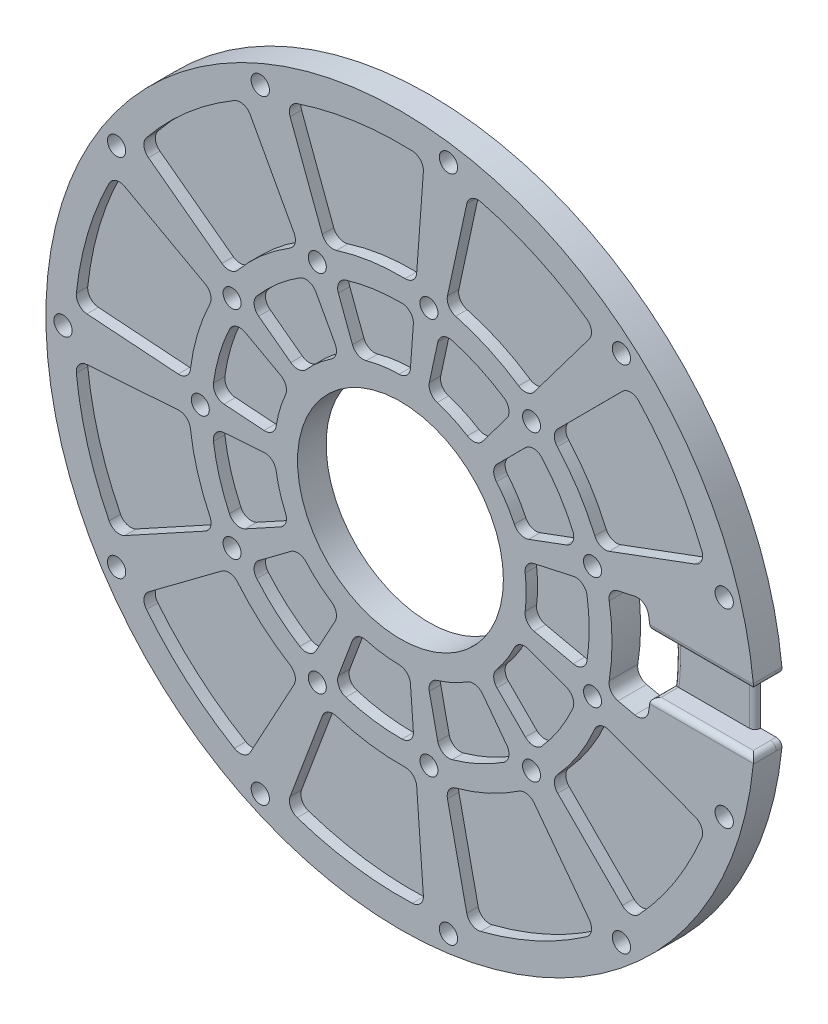
SolidWorks part; units mm, degrees
material "ABS"
ref_plane "Front Plane" through (0, 0, 0) normal (0, 0, 1) x (1, 0, 0)
ref_plane "Top Plane" through (0, 0, 0) normal (0, 1, 0) x (1, 0, 0)
ref_plane "Right Plane" through (0, 0, 0) normal (1, 0, 0) x (0, 0, -1)
sketch "Sketch1" plane through (0, 0, -61.9958) normal (0, 0, 1) x (1, 0, 0)
  circle A0 centre (89.0728, 47.2587) radius 62
  circle A2 centre (89.0728, 47.2587) radius 18
  dimension "D1" = 124
  dimension "D2" = 36
extrude "Boss-Extrude1" add sketch "Sketch1" along normal blind 5
sketch "Sketch2" plane through (0, 0, -56.9958) normal (0, 0, 1) x (1, 0, 0)
  line L0 (89.0728, 47.2587) -> (54.0728, 47.2587) construction
  circle A0 centre (54.0728, 47.2587) radius 1.575
  circle A1 centre (59.6289, 66.1811) radius 1.575
  circle A2 centre (74.5333, 79.0958) radius 1.575
  circle A3 centre (94.0538, 81.9025) radius 1.575
  circle A4 centre (111.9929, 73.7099) radius 1.575
  circle A5 centre (122.655, 57.1193) radius 1.575
  circle A6 centre (122.655, 37.3981) radius 1.575
  circle A7 centre (111.9929, 20.8075) radius 1.575
  circle A8 centre (94.0538, 12.615) radius 1.575
  circle A9 centre (74.5333, 15.4216) radius 1.575
  circle A10 centre (59.6289, 28.3363) radius 1.575
  point P27 (89.0728, 47.2587)
  dimension "D2" = 3.15
  dimension "D3" = 11
  dimension "D1" = 35
extrude "Cut-Extrude1" cut sketch "Sketch2" against normal through all
sketch "Sketch4" plane through (0, 0, -56.9958) normal (0, 0, 1) x (1, 0, 0)
  line L0 (89.0728, 47.2587) -> (30.0728, 47.2587) construction
  circle A0 centre (30.0728, 47.2587) radius 1.6
  circle A1 centre (39.4388, 79.1565) radius 1.6
  circle A2 centre (64.5633, 100.927) radius 1.6
  circle A3 centre (97.4694, 105.6582) radius 1.6
  circle A4 centre (127.7096, 91.8479) radius 1.6
  circle A5 centre (145.6829, 63.8809) radius 1.6
  circle A6 centre (145.6829, 30.6365) radius 1.6
  circle A7 centre (127.7096, 2.6695) radius 1.6
  circle A8 centre (97.4694, -11.1408) radius 1.6
  circle A9 centre (64.5633, -6.4096) radius 1.6
  circle A10 centre (39.4388, 15.3609) radius 1.6
  point P28 (89.0728, 47.2587)
  dimension "D2" = 3.2
  dimension "D1" = 59
  dimension "D3" = 11
extrude "Cut-Extrude3" cut sketch "Sketch4" against normal through all
sketch "Sketch3" plane through (0, 0, -56.9958) normal (0, 0, 1) x (1, 0, 0)
  line L0 (89.0728, 47.2587) -> (94.0538, 81.9025) construction
  line L1 (89.0728, 47.2587) -> (74.5333, 79.0958) construction
  line L2 (78.216, 76.2264) -> (80.6793, 69.654)
  line L3 (91.3287, 78.1118) -> (90.8168, 71.1116)
  line L44 (89.0728, 47.2587) -> (64.5633, 100.927) construction
  line L45 (89.0728, 47.2587) -> (97.4694, 105.6582) construction
  line L46 (75.4037, 83.73) -> (69.7833, 98.7263)
  line L47 (93.0808, 102.076) -> (91.913, 86.1037)
  line L52 (127.1182, 55.5982) -> (130.0522, 56.2414)
  line L53 (130.0522, 38.2761) -> (127.1182, 38.9192)
  line L68 (122.081, 91.207) -> (112.4633, 78.4017)
  line L69 (97.2915, 85.3304) -> (100.6709, 100.9847)
  line L70 (140.6014, 66.3848) -> (125.5873, 60.812)
  line L71 (116.5699, 74.8433) -> (127.8762, 86.1855)
  line L72 (142.7617, 35.4901) -> (127.1182, 38.9192) [skipped]
  line L73 (127.1182, 55.5982) -> (142.7617, 59.0273) [skipped]
  line L74 (127.8762, 8.3319) -> (116.5699, 19.6742)
  line L75 (125.5873, 33.7055) -> (140.6014, 28.1326)
  line L76 (100.6709, -6.4673) -> (97.2915, 9.187)
  line L77 (112.4633, 16.1158) -> (122.081, 3.3104)
  line L78 (69.7833, -4.2089) -> (75.4037, 10.7874)
  line L79 (91.913, 8.4137) -> (93.0808, -7.5586)
  line L80 (45.0199, 14.3901) -> (57.8558, 23.9671)
  line L81 (70.4609, 13.0447) -> (62.8081, -1.0234)
  line L82 (34.2431, 43.4246) -> (50.219, 44.5418)
  line L83 (54.918, 28.5384) -> (40.8742, 20.8409)
  line L84 (40.8742, 73.6765) -> (54.918, 65.979)
  line L85 (50.219, 49.9756) -> (34.2431, 51.0928)
  line L86 (62.8081, 95.5409) -> (70.4609, 81.4727)
  line L87 (57.8558, 70.5503) -> (45.0199, 80.1273)
  line L88 (95.6006, 77.4975) -> (94.1195, 70.6367)
  line L89 (107.651, 71.9943) -> (103.4358, 66.3821)
  line L90 (110.9127, 69.168) -> (105.9575, 64.1971)
  line L91 (118.0748, 58.0235) -> (111.4946, 55.5811)
  line L92 (119.2908, 53.8825) -> (112.4347, 52.3796)
  line L93 (119.2908, 40.635) -> (112.4347, 42.1378)
  line L94 (118.0748, 36.4939) -> (111.4946, 38.9363)
  line L95 (110.9127, 25.3494) -> (105.9575, 30.3204)
  line L96 (107.651, 22.5231) -> (103.4358, 28.1353)
  line L97 (95.6006, 17.0199) -> (94.1195, 23.8807)
  line L98 (91.3287, 16.4057) -> (90.8168, 23.4059)
  line L99 (78.216, 18.291) -> (80.6793, 24.8634)
  line L100 (74.2901, 20.0839) -> (77.6441, 26.2495)
  line L101 (64.2783, 28.7591) -> (69.9039, 32.9565)
  line L102 (61.945, 32.3899) -> (68.1, 35.7634)
  line L103 (58.2127, 45.1008) -> (65.2145, 45.5904)
  line L104 (58.2127, 49.4167) -> (65.2145, 48.927)
  line L105 (61.945, 62.1275) -> (68.1, 58.754)
  line L106 (64.2783, 65.7583) -> (69.9039, 61.5609)
  line L107 (74.2901, 74.4336) -> (77.6441, 68.2679)
  arc A0 (88.843, 69.2575) -> (83.0955, 68.4311) centre (89.0728, 47.2587) ccw
  arc A1 (89.3508, 80.2575) -> (79.5092, 78.8425) centre (89.0728, 47.2587) ccw
  arc A22 (91.3287, 78.1118) -> (89.3508, 80.2575) centre (89.334, 78.2576) ccw
  arc A23 (78.216, 76.2264) -> (79.5092, 78.8425) centre (80.0888, 76.9283) cw
  arc A24 (80.6793, 69.654) -> (83.0955, 68.4311) centre (82.5521, 70.3559) ccw
  arc A25 (90.8168, 71.1116) -> (88.843, 69.2575) centre (88.8222, 71.2574) cw
  arc A86 (77.8815, 82.5256) -> (89.875, 84.25) centre (89.0728, 47.2587) cw
  arc A87 (71.0227, 101.3253) -> (91.1594, 104.2205) centre (89.0728, 47.2587) cw
  arc A88 (91.913, 86.1037) -> (89.875, 84.25) centre (89.9183, 86.2495) cw
  arc A89 (93.0808, 102.076) -> (91.1594, 104.2205) centre (91.0862, 102.2218) ccw
  arc A90 (69.7833, 98.7263) -> (71.0227, 101.3253) centre (71.6561, 99.4282) cw
  arc A91 (75.4037, 83.73) -> (77.8815, 82.5256) centre (77.2765, 84.4319) ccw
  arc A104 (132.4522, 54.6225) -> (132.4522, 39.895) centre (89.0728, 47.2587) cw
  arc A106 (127.1182, 55.5982) -> (125.5734, 53.3171) centre (127.5464, 53.6446) ccw
  arc A107 (125.5734, 53.3171) -> (125.5734, 41.2003) centre (89.0728, 47.2587) cw
  arc A108 (127.1182, 38.9192) -> (125.5734, 41.2003) centre (127.5464, 40.8728) cw
  arc A152 (132.4522, 54.6225) -> (130.0522, 56.2414) centre (130.4804, 54.2877) ccw
  arc A153 (132.4522, 39.895) -> (130.0522, 38.2761) centre (130.4804, 40.2297) cw
  arc A154 (122.081, 91.207) -> (121.624, 94.0499) centre (120.4819, 92.4081) ccw
  arc A155 (103.1187, 102.501) -> (121.624, 94.0499) centre (89.0728, 47.2587) cw
  arc A156 (100.6709, 100.9847) -> (103.1187, 102.501) centre (102.6259, 100.5627) cw
  arc A157 (97.2915, 85.3304) -> (98.7248, 82.9776) centre (99.2465, 84.9084) ccw
  arc A158 (98.7248, 82.9776) -> (109.7466, 77.9441) centre (89.0728, 47.2587) cw
  arc A159 (112.4633, 78.4017) -> (109.7466, 77.9441) centre (110.8641, 79.6028) cw
  arc A160 (140.6014, 66.3848) -> (141.7539, 69.0235) centre (139.9054, 68.2598) ccw
  arc A161 (130.7552, 86.1377) -> (141.7539, 69.0235) centre (89.0728, 47.2587) cw
  arc A162 (127.8762, 86.1855) -> (130.7552, 86.1377) centre (129.2927, 84.7735) cw
  arc A163 (116.5699, 74.8433) -> (116.5036, 72.0891) centre (117.9864, 73.4313) ccw
  arc A164 (116.5036, 72.0891) -> (123.0545, 61.8958) centre (89.0728, 47.2587) cw
  arc A165 (125.5873, 60.812) -> (123.0545, 61.8958) centre (124.8913, 62.687) cw
  arc A166 (142.7617, 35.4901) -> (145.1578, 37.0869) centre (143.19, 37.4438) ccw [skipped]
  arc A167 (145.1578, 57.4306) -> (145.1578, 37.0869) centre (89.0728, 47.2587) cw [skipped]
  arc A168 (142.7617, 59.0273) -> (145.1578, 57.4306) centre (143.19, 57.0737) cw [skipped]
  arc A169 (127.1182, 55.5982) -> (125.5734, 53.3171) centre (127.5464, 53.6446) ccw [skipped]
  arc A170 (125.5734, 53.3171) -> (125.5734, 41.2003) centre (89.0728, 47.2587) cw [skipped]
  arc A171 (127.1182, 38.9192) -> (125.5734, 41.2003) centre (127.5464, 40.8728) cw [skipped]
  arc A172 (127.8762, 8.3319) -> (130.7552, 8.3797) centre (129.2927, 9.7439) ccw
  arc A173 (141.7539, 25.4939) -> (130.7552, 8.3797) centre (89.0728, 47.2587) cw
  arc A174 (140.6014, 28.1326) -> (141.7539, 25.4939) centre (139.9054, 26.2576) cw
  arc A175 (125.5873, 33.7055) -> (123.0545, 32.6216) centre (124.8913, 31.8305) ccw
  arc A176 (123.0545, 32.6216) -> (116.5036, 22.4283) centre (89.0728, 47.2587) cw
  arc A177 (116.5699, 19.6742) -> (116.5036, 22.4283) centre (117.9864, 21.0861) cw
  arc A178 (100.6709, -6.4673) -> (103.1187, -7.9836) centre (102.6259, -6.0453) ccw
  arc A179 (121.624, 0.4675) -> (103.1187, -7.9836) centre (89.0728, 47.2587) cw
  arc A180 (122.081, 3.3104) -> (121.624, 0.4675) centre (120.4819, 2.1093) cw
  arc A181 (112.4633, 16.1158) -> (109.7466, 16.5733) centre (110.8641, 14.9147) ccw
  arc A182 (109.7466, 16.5733) -> (98.7248, 11.5398) centre (89.0728, 47.2587) cw
  arc A183 (97.2915, 9.187) -> (98.7248, 11.5398) centre (99.2465, 9.6091) cw
  arc A184 (69.7833, -4.2089) -> (71.0227, -6.8079) centre (71.6561, -4.9108) ccw
  arc A185 (91.1594, -9.7031) -> (71.0227, -6.8079) centre (89.0728, 47.2587) cw
  arc A186 (93.0808, -7.5586) -> (91.1594, -9.7031) centre (91.0862, -7.7044) cw
  arc A187 (91.913, 8.4137) -> (89.875, 10.2674) centre (89.9183, 8.2679) ccw
  arc A188 (89.875, 10.2674) -> (77.8815, 11.9918) centre (89.0728, 47.2587) cw
  arc A189 (75.4037, 10.7874) -> (77.8815, 11.9918) centre (77.2765, 10.0855) cw
  arc A190 (45.0199, 14.3901) -> (44.6575, 11.5336) centre (46.216, 12.7871) ccw
  arc A191 (60.0323, -1.7887) -> (44.6575, 11.5336) centre (89.0728, 47.2587) cw
  arc A192 (62.8081, -1.0234) -> (60.0323, -1.7887) centre (61.0512, -0.0677) cw
  arc A193 (70.4609, 13.0447) -> (69.7486, 15.706) centre (68.7041, 14.0004) ccw
  arc A194 (69.7486, 15.706) -> (60.5913, 23.6408) centre (89.0728, 47.2587) cw
  arc A195 (57.8558, 23.9671) -> (60.5913, 23.6408) centre (59.0518, 22.3642) cw
  arc A196 (34.2431, 43.4246) -> (32.3938, 41.2175) centre (34.3826, 41.4295) ccw
  arc A197 (38.1253, 21.6979) -> (32.3938, 41.2175) centre (89.0728, 47.2587) cw
  arc A198 (40.8742, 20.8409) -> (38.1253, 21.6979) centre (39.9129, 22.5948) cw
  arc A199 (54.918, 28.5384) -> (55.7576, 31.1623) centre (53.9567, 30.2922) ccw
  arc A200 (55.7576, 31.1623) -> (52.3438, 42.7883) centre (89.0728, 47.2587) cw
  arc A201 (50.219, 44.5418) -> (52.3438, 42.7883) centre (50.3585, 42.5467) cw
  arc A202 (40.8742, 73.6765) -> (38.1253, 72.8195) centre (39.9129, 71.9226) ccw
  arc A203 (32.3938, 53.2999) -> (38.1253, 72.8195) centre (89.0728, 47.2587) cw
  arc A204 (34.2431, 51.0928) -> (32.3938, 53.2999) centre (34.3826, 53.0879) cw
  arc A205 (50.219, 49.9756) -> (52.3438, 51.7291) centre (50.3585, 51.9708) ccw
  arc A206 (52.3438, 51.7291) -> (55.7576, 63.3551) centre (89.0728, 47.2587) cw
  arc A207 (54.918, 65.979) -> (55.7576, 63.3551) centre (53.9567, 64.2252) cw
  arc A208 (62.8081, 95.5409) -> (60.0323, 96.3061) centre (61.0512, 94.5851) ccw
  arc A209 (44.6575, 82.9838) -> (60.0323, 96.3061) centre (89.0728, 47.2587) cw
  arc A210 (45.0199, 80.1273) -> (44.6575, 82.9838) centre (46.216, 81.7303) cw
  arc A211 (57.8558, 70.5503) -> (60.5913, 70.8766) centre (59.0518, 72.1533) ccw
  arc A212 (60.5913, 70.8766) -> (69.7486, 78.8115) centre (89.0728, 47.2587) cw
  arc A213 (70.4609, 81.4727) -> (69.7486, 78.8115) centre (68.7041, 80.517) cw
  arc A214 (107.1472, 74.8688) -> (98.1029, 78.9992) centre (89.0728, 47.2587) ccw
  arc A215 (95.6006, 77.4975) -> (98.1029, 78.9992) centre (97.5556, 77.0755) cw
  arc A216 (100.773, 65.8895) -> (95.491, 68.3017) centre (89.0728, 47.2587) ccw
  arc A217 (94.1195, 70.6367) -> (95.491, 68.3017) centre (96.0745, 70.2147) ccw
  arc A218 (103.4358, 66.3821) -> (100.773, 65.8895) centre (101.8366, 67.5832) cw
  arc A219 (107.651, 71.9943) -> (107.1472, 74.8688) centre (106.0518, 73.1954) ccw
  arc A220 (119.2051, 60.714) -> (113.8296, 69.0785) centre (89.0728, 47.2587) ccw
  arc A221 (110.9127, 69.168) -> (113.8296, 69.0785) centre (112.3292, 67.7561) cw
  arc A222 (108.9882, 56.6063) -> (105.8488, 61.4912) centre (89.0728, 47.2587) ccw
  arc A223 (105.9575, 64.1971) -> (105.8488, 61.4912) centre (107.3739, 62.7851) ccw
  arc A224 (111.4946, 55.5811) -> (108.9882, 56.6063) centre (110.7986, 57.4561) cw
  arc A225 (118.0748, 58.0235) -> (119.2051, 60.714) centre (117.3789, 59.8985) ccw
  arc A226 (121.6962, 42.2873) -> (121.6962, 52.2301) centre (89.0728, 47.2587) ccw
  arc A227 (119.2908, 53.8825) -> (121.6962, 52.2301) centre (119.719, 51.9288) cw
  arc A228 (110.8804, 44.3554) -> (110.8804, 50.162) centre (89.0728, 47.2587) ccw
  arc A229 (112.4347, 52.3796) -> (110.8804, 50.162) centre (112.8629, 50.426) ccw
  arc A230 (112.4347, 42.1378) -> (110.8804, 44.3554) centre (112.8629, 44.0914) cw
  arc A231 (119.2908, 40.635) -> (121.6962, 42.2873) centre (119.719, 42.5886) ccw
  arc A232 (113.8296, 25.4389) -> (119.2051, 33.8034) centre (89.0728, 47.2587) ccw
  arc A233 (118.0748, 36.4939) -> (119.2051, 33.8034) centre (117.3789, 34.6189) cw
  arc A234 (105.8488, 33.0262) -> (108.9882, 37.9111) centre (89.0728, 47.2587) ccw
  arc A235 (111.4946, 38.9363) -> (108.9882, 37.9111) centre (110.7986, 37.0613) ccw
  arc A236 (105.9575, 30.3204) -> (105.8488, 33.0262) centre (107.3739, 31.7323) cw
  arc A237 (110.9127, 25.3494) -> (113.8296, 25.4389) centre (112.3292, 26.7614) ccw
  arc A238 (98.1029, 15.5182) -> (107.1472, 19.6486) centre (89.0728, 47.2587) ccw
  arc A239 (107.651, 22.5231) -> (107.1472, 19.6486) centre (106.0518, 21.322) cw
  arc A240 (95.491, 26.2157) -> (100.773, 28.6279) centre (89.0728, 47.2587) ccw
  arc A241 (103.4358, 28.1353) -> (100.773, 28.6279) centre (101.8366, 26.9342) ccw
  arc A242 (94.1195, 23.8807) -> (95.491, 26.2157) centre (96.0745, 24.3027) cw
  arc A243 (95.6006, 17.0199) -> (98.1029, 15.5182) centre (97.5556, 17.4419) ccw
  arc A244 (79.5092, 15.6749) -> (89.3508, 14.2599) centre (89.0728, 47.2587) ccw
  arc A245 (91.3287, 16.4057) -> (89.3508, 14.2599) centre (89.334, 16.2598) cw
  arc A246 (83.0955, 26.0863) -> (88.843, 25.2599) centre (89.0728, 47.2587) ccw
  arc A247 (90.8168, 23.4059) -> (88.843, 25.2599) centre (88.8222, 23.26) ccw
  arc A248 (80.6793, 24.8634) -> (83.0955, 26.0863) centre (82.5521, 24.1615) cw
  arc A249 (78.216, 18.291) -> (79.5092, 15.6749) centre (80.0888, 17.5891) ccw
  arc A250 (63.9519, 25.8592) -> (71.4662, 19.348) centre (89.0728, 47.2587) ccw
  arc A251 (74.2901, 20.0839) -> (71.4662, 19.348) centre (72.5332, 21.0396) cw
  arc A252 (72.5977, 32.6789) -> (76.9861, 28.8764) centre (89.0728, 47.2587) ccw
  arc A253 (77.6441, 26.2495) -> (76.9861, 28.8764) centre (75.8873, 27.2052) ccw
  arc A254 (69.9039, 32.9565) -> (72.5977, 32.6789) centre (71.0999, 31.3535) cw
  arc A255 (64.2783, 28.7591) -> (63.9519, 25.8592) centre (65.4743, 27.1561) ccw
  arc A256 (56.3703, 42.8377) -> (59.1715, 33.2976) centre (89.0728, 47.2587) ccw
  arc A257 (61.945, 32.3899) -> (59.1715, 33.2976) centre (60.9837, 34.1437) cw
  arc A258 (67.3306, 43.9005) -> (68.9665, 38.3291) centre (89.0728, 47.2587) ccw
  arc A259 (68.1, 35.7634) -> (68.9665, 38.3291) centre (67.1387, 37.5173) ccw
  arc A260 (65.2145, 45.5904) -> (67.3306, 43.9005) centre (65.354, 43.5952) cw
  arc A261 (58.2127, 45.1008) -> (56.3703, 42.8377) centre (58.3522, 43.1056) ccw
  arc A262 (59.1715, 61.2198) -> (56.3703, 51.6797) centre (89.0728, 47.2587) ccw
  arc A263 (58.2127, 49.4167) -> (56.3703, 51.6797) centre (58.3522, 51.4118) cw
  arc A264 (68.9665, 56.1883) -> (67.3306, 50.6169) centre (89.0728, 47.2587) ccw
  arc A265 (65.2145, 48.927) -> (67.3306, 50.6169) centre (65.354, 50.9222) ccw
  arc A266 (68.1, 58.754) -> (68.9665, 56.1883) centre (67.1387, 57.0001) cw
  arc A267 (61.945, 62.1275) -> (59.1715, 61.2198) centre (60.9837, 60.3737) ccw
  arc A268 (71.4662, 75.1694) -> (63.9519, 68.6582) centre (89.0728, 47.2587) ccw
  arc A269 (64.2783, 65.7583) -> (63.9519, 68.6582) centre (65.4743, 67.3613) cw
  arc A270 (76.9861, 65.6411) -> (72.5977, 61.8385) centre (89.0728, 47.2587) ccw
  arc A271 (69.9039, 61.5609) -> (72.5977, 61.8385) centre (71.0999, 63.1639) ccw
  arc A272 (77.6441, 68.2679) -> (76.9861, 65.6411) centre (75.8873, 67.3122) cw
  arc A273 (74.2901, 74.4336) -> (71.4662, 75.1694) centre (72.5332, 73.4779) ccw
  point P52 (89.0728, 47.2587)
  point P142 (89.0728, 47.2587)
  point P291 (89.0728, 47.2587)
  point P293 (89.0728, 47.2587)
  dimension "D1" = 33
  dimension "D2" = 22
  dimension "D5" = 44
  dimension "D6" = 6.5725
  dimension "D7" = 57
  dimension "D8" = 37
  dimension "D11" = 2
  dimension "D12" = 2
  dimension "D13" = 11
  dimension "D14" = 3.0037
  dimension "D10" = 15.9723
  dimension "D4" = 7.0002
  dimension "D3" = 2
  dimension "D15" = 37
  dimension "D16" = 11
  dimension "D9" = 4
extrude "Cut-Extrude2" cut sketch "Sketch3" against normal blind 2
extrude "Cut-Extrude5" cut sketch "Sketch3<3>" against normal through all contours A153 A104 A152 L52 A106 A107 A108 L53 region at (129.3712, 47.2587, -56.9958)
sketch "Sketch3<3>" plane through (0, 0, -56.9958) normal (0, 0, 1) x (1, 0, 0) same geometry as "Sketch3"
sketch "Sketch7" plane through (0, 0, -56.9958) normal (0, 0, 1) x (1, 0, 0)
  line L0 (133.0728, 47.2587) -> (151.0728, 47.2587) construction
  line L1 (132.7878, 52.2587) -> (151.0728, 52.2587)
  line L2 (132.7878, 42.2587) -> (151.0728, 42.2587)
  line L3 (132.7878, 52.2587) -> (132.7878, 42.2587)
  line L4 (151.0728, 47.2587) -> (151.0728, 52.2587)
  line L5 (151.0728, 47.2587) -> (151.0728, 42.2587)
  arc A0 (132.4522, 39.895) -> (132.4522, 54.6225) centre (89.0728, 47.2587) ccw construction
  circle A1 centre (89.0728, 47.2587) radius 62 construction
  dimension "D1" = 5
  dimension "D2" = 5
extrude "Cut-Extrude6" cut sketch "Sketch7" against normal blind 4 contours L4 L1 L3 L2 L5
fillet "Fillet1" radius 1 7 edges at (132.7878, 42.2587, -58.9958) (150.8709, 42.2587, -58.9958) (132.7878, 52.2587, -58.9958) (150.8709, 52.2587, -58.9958) (133.0728, 47.2587, -60.9958) (141.8293, 52.2587, -56.9958) (141.8293, 42.2587, -56.9958)
sketch "Sketch8" plane through (0, 0, -60.9958) normal (0, 0, 1) x (1, 0, 0)
  line L0 (149.777, 52.2587) -> (133.671, 52.2587) construction
  line L1 (155.0728, 42.2587) -> (147.0728, 42.2587)
  line L2 (155.0728, 42.2587) -> (155.0728, 52.2587)
  line L3 (155.0728, 52.2587) -> (147.0728, 52.2587)
  line L4 (147.0728, 42.2587) -> (147.0728, 52.2587)
  line L5 (155.0728, 42.2587) -> (147.0728, 52.2587) construction
  line L6 (155.0728, 52.2587) -> (147.0728, 42.2587) construction
  arc A0 (150.7721, 41.1603) -> (150.7721, 53.3571) centre (89.0728, 47.2587) ccw construction
  point P0 (151.0728, 47.2587)
  dimension "D1" = 8
extrude "Cut-Extrude7" cut sketch "Sketch8" against normal through all
fillet "Fillet2" radius 1 2 edges at (150.8709, 42.2587, -61.4958) (150.8709, 52.2587, -61.4958)
fillet "Fillet3" radius 1 1 edges at (147.0728, 47.2587, -60.9958)
equation "\"HousingIn\"=113"
equation "\"HousingOut\"=124"
equation "\"FrontCutout\"=36"
equation "\"D1@Sketch1\"=\"HousingOut\""
equation "\"D2@Sketch1\"=\"FrontCutout\""
equation "\"D1@Sketch4\"=\"HousingOut\"/2 -3"
